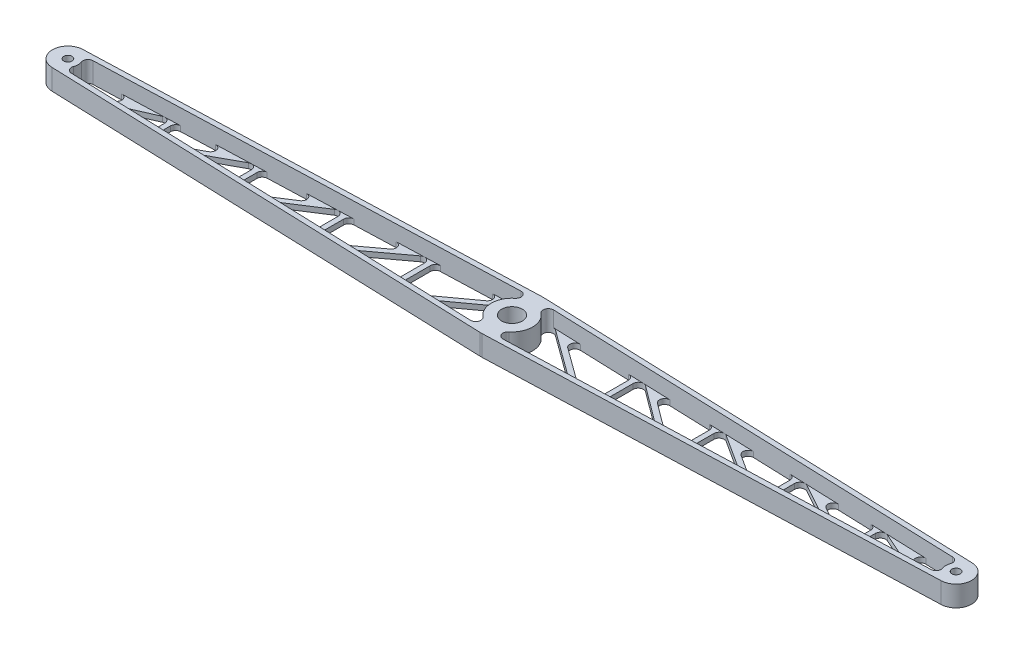
SolidWorks part; units mm, degrees
material "6061 Alloy"
ref_plane "Front Plane" through (0, 0, 0) normal (0, 0, 1) x (1, 0, 0)
ref_plane "Top Plane" through (0, 0, 0) normal (0, 1, 0) x (1, 0, 0)
ref_plane "Right Plane" through (0, 0, 0) normal (1, 0, 0) x (0, 0, -1)
sketch "Sketch1" plane through (0, 0, 0) normal (1, 0, 0) x (0, 0, -1)
  line L1 (-19.05, -6.35) -> (19.05, -6.35)
  line L2 (-19.05, -6.35) -> (-19.05, 6.35)
  line L3 (-19.05, 6.35) -> (19.05, 6.35)
  line L4 (19.05, -6.35) -> (19.05, 6.35)
  line L5 (-19.05, -6.35) -> (19.05, 6.35) construction
  line L6 (-19.05, 6.35) -> (19.05, -6.35) construction
  point P0 (0, 0)
  dimension "D1" = 38.1
  dimension "D2" = 12.7
extrude "Boss-Extrude1" add sketch "Sketch1" along normal mid plane 584.2
sketch "Sketch2" plane through (0, 6.35, 0) normal (0, 1, 0) x (1, 0, 0)
  circle A0 centre (0, 0) radius 6.35
  dimension "D1" = 12.7
extrude "Pivot Hole" cut sketch "Sketch2" against normal through all
hole_wizard "End Holes" positions "Sketch4" profile "Sketch3" tap size "1/4-20" standard "ANSI Inch" end condition through all
sketch "Sketch4" plane through (0, -6.35, 0) normal (0, -1, 0) x (-1, 0, 0)
  line L0 (273.05, 0) -> (292.1, 0) construction
  line L1 (292.1, -19.05) -> (292.1, 19.05) construction
  line L4 (-273.05, 0) -> (-292.1, 0) construction
  line L5 (-292.1, -19.05) -> (-292.1, 19.05) construction
  point P0 (273.05, 0)
  point P2 (-273.05, 0)
  dimension "D1" = 19.05
sketch "Sketch3" plane through (-273.05, -6.35, 0) normal (1, 0, 0) x (0, 0, -1)
  line L0 (0, 0) -> (0, 12.7)
  line L1 (0, 12.7) -> (2.5527, 12.7)
  line L2 (2.5527, 12.7) -> (2.5527, 0)
  line L5 (2.5527, 0) -> (0, 0)
  line L11 (0, -6.35) -> (0, 107.95) construction
  dimension "Thread Major Dia." = 5.1054
  dimension "Thru Tap Drill Depth" = 12.7
sketch "Sketch5" plane through (0, 6.35, 0) normal (0, 1, 0) x (1, 0, 0)
  line L0 (273.3823, -9.5192) -> (0.6645, -19.0384)
  line L1 (0.6645, 19.0384) -> (273.3823, 9.5192)
  line L2 (-0.6645, -19.0384) -> (-273.3823, -9.5192)
  line L3 (-273.3823, 9.5192) -> (-0.6645, 19.0384)
  line L8 (-292.1, 19.05) -> (-292.1, -19.05)
  line L9 (-292.1, -19.05) -> (292.1, -19.05)
  line L10 (292.1, -19.05) -> (292.1, 19.05)
  line L11 (292.1, 19.05) -> (-292.1, 19.05)
  line L12 (-292.1, 19.05) -> (-292.1, -19.05)
  line L13 (-292.1, -19.05) -> (292.1, -19.05)
  line L14 (292.1, -19.05) -> (292.1, 19.05)
  line L15 (292.1, 19.05) -> (-292.1, 19.05)
  arc A0 (273.3823, -9.5192) -> (273.3823, 9.5192) centre (273.05, 0) ccw
  arc A1 (-273.3823, -9.5192) -> (-273.3823, 9.5192) centre (-273.05, 0) cw
  arc A2 (0.6645, -19.0384) -> (-0.6645, -19.0384) centre (0, 0) cw
  arc A3 (-0.6645, 19.0384) -> (0.6645, 19.0384) centre (0, 0) cw
  line M8 (-292.1, 19.05) -> (-292.1, -19.05)
  line M9 (-292.1, -19.05) -> (292.1, -19.05)
  line M10 (292.1, -19.05) -> (292.1, 19.05)
  line M11 (292.1, 19.05) -> (-292.1, 19.05)
  dimension "D1" = 9.525
  dimension "D2" = 19.05
  dimension "D3" = 0
extrude "Profile Cut" cut sketch "Sketch5" against normal through all contours A3 L1 A0 L0 A2 L13 M11 M10 | L3 A3 L15 A2 L2 A1 M8 M9 region at (285.5207, 6.35, 0) region at (-146.05, 6.35, 16.1043)
sketch "Sketch7" plane through (0, 6.35, 0) normal (0, 1, 0) x (1, 0, 0)
  line L18 (0.5538, 15.8653) -> (273.2715, 6.3461)
  line L19 (10.073, 15.5331) -> (264.2967, 6.6594)
  line L25 (273.2715, -6.3461) -> (0.5538, -15.8653)
  line L26 (264.2967, -6.6594) -> (10.073, -15.5331)
  line L28 (-0.5538, -15.8653) -> (-273.2715, -6.3461)
  line L29 (-10.073, -15.5331) -> (-264.2967, -6.6594)
  line L31 (-273.2715, 6.3461) -> (-0.5538, 15.8653)
  line L32 (-264.2967, 6.6594) -> (-10.073, 15.5331)
  arc A0 (267.1406, 2.3242) -> (267.1406, -2.3242) centre (273.05, 0) ccw
  arc A1 (-267.1406, -2.3242) -> (-267.1406, 2.3242) centre (-273.05, 0) ccw
  arc A2 (7.9698, 9.888) -> (7.9698, -9.888) centre (0, 0) cw
  arc A3 (-7.9698, 9.888) -> (-7.9698, -9.888) centre (0, 0) ccw
  arc A4 (-267.1406, 2.3242) -> (-264.2967, 6.6594) centre (-264.186, 3.4863) cw
  arc A5 (-264.2967, -6.6594) -> (-267.1406, -2.3242) centre (-264.186, -3.4863) cw
  arc A6 (267.1406, -2.3242) -> (264.2967, -6.6594) centre (264.186, -3.4863) cw
  arc A7 (264.2967, 6.6594) -> (267.1406, 2.3242) centre (264.186, 3.4863) cw
  arc A8 (10.073, 15.5331) -> (7.9698, 9.888) centre (9.9622, 12.36) ccw
  arc A9 (7.9698, -9.888) -> (10.073, -15.5331) centre (9.9622, -12.36) ccw
  arc A10 (-7.9698, -9.888) -> (-10.073, -15.5331) centre (-9.9622, -12.36) cw
  arc A11 (-10.073, 15.5331) -> (-7.9698, 9.888) centre (-9.9622, 12.36) cw
  dimension "D5" = 6.35
  dimension "D6" = 3.175
  dimension "D7" = 12.7
  dimension "D1" = 3.175
  dimension "D2" = 3.175
  dimension "D3" = 3.175
  dimension "D4" = 3.175
extrude "Pocket" cut sketch "Sketch7" against normal offset from surface (9.525 mm away) 3.175 up to face at (-273.05, -6.35, -2.5527)
sketch "Sketch6" plane through (0, 6.35, 0) normal (0, 1, 0) x (1, 0, 0)
  line L0 (0, 19.05) -> (0, -19.05) construction
  line L1 (0, 15.8847) -> (-273.3823, 6.3423) construction
  line L2 (0, -15.8847) -> (-273.3823, -6.3423) construction
  line L3 (-273.3823, 9.5192) -> (-0.6645, 19.0384) construction
  line L4 (-0.6645, -19.0384) -> (-273.3823, -9.5192) construction
  line L5 (-136.6911, 11.1135) -> (-136.8019, 14.2865) construction
  line L6 (-136.6911, -11.1135) -> (-136.8019, -14.2865) construction
  line L7 (-273.3823, 9.5192) -> (-273.3823, -9.5192) construction
  line L8 (-44.2165, -8.6633) -> (-11.8316, 14.9263)
  line L9 (-262.8989, -6.3888) -> (-245.8319, 1.1796)
  line L10 (-247.2297, 7.2551) -> (-264.2967, 6.6594)
  line L11 (-243.6911, -1.3442) -> (-222.9021, 7.8747)
  line L12 (-218.44, 4.9723) -> (-218.44, -4.9723)
  line L13 (-221.7258, -8.1453) -> (-242.5148, -7.4197)
  line L14 (-245.8319, 1.1796) -> (-244.5448, -1.7228) construction
  line L15 (-215.265, 5.3047) -> (-215.265, -5.3047)
  line L16 (-210.5661, -8.0901) -> (-189.8531, 3.2424)
  line L17 (-191.4878, 9.2008) -> (-212.2008, 8.4778)
  line L18 (-194.9594, -3.1705) -> (-171.7039, 9.553)
  line L19 (-167.005, 6.7676) -> (-167.005, -6.7676)
  line L20 (-170.2908, -9.9407) -> (-193.5462, -9.1289)
  line L21 (-189.8531, 3.2424) -> (-188.3292, 0.457) construction
  line L22 (-218.44, 0) -> (-215.265, 0) construction
  line L23 (-10.073, -15.5331) -> (-42.4579, -14.4027)
  line L24 (-60.96, -10.6908) -> (-60.96, 10.6908)
  line L25 (-57.8958, 13.8638) -> (-27.0649, 14.94)
  line L26 (-25.0848, 9.2006) -> (-55.9156, -13.2571)
  line L27 (-25.0848, 9.2006) -> (-23.2154, 6.6342) construction
  line L28 (-163.83, 7.1001) -> (-163.83, -7.1001)
  line L29 (-158.9358, -9.7694) -> (-135.6247, 5.2445)
  line L30 (-137.4546, 11.0868) -> (-160.7658, 10.2731)
  line L31 (-145.6876, -5.0132) -> (-120.4642, 11.2322)
  line L32 (-115.57, 8.5629) -> (-115.57, -8.5629)
  line L33 (-118.8558, -11.736) -> (-144.0792, -10.8556)
  line L34 (-135.6247, 5.2445) -> (-133.9055, 2.5752) construction
  line L35 (-167.005, 0) -> (-163.83, 0) construction
  line L36 (-266.7, 0) -> (-218.44, 0) construction
  line L37 (-215.265, 0) -> (-167.005, 0) construction
  line L38 (-163.83, 0) -> (-115.57, 0) construction
  line L39 (-60.96, 0) -> (-12.7, 0) construction
  line L40 (-115.57, 0) -> (-112.395, 0) construction
  line L41 (-64.135, 0) -> (-60.96, 0) construction
  line L42 (-112.395, 8.8954) -> (-112.395, -8.8954)
  line L43 (-107.3273, -11.4446) -> (-82.1837, 7.2239)
  line L44 (-84.1872, 12.9461) -> (-109.3308, 12.0685)
  line L45 (-95.852, -6.8789) -> (-69.2027, 12.9075)
  line L46 (-64.135, 10.3583) -> (-64.135, -10.3583)
  line L47 (-67.4208, -13.5313) -> (-94.07, -12.6012)
  line L48 (-82.1837, 7.2239) -> (-80.291, 4.6747) construction
  line L49 (-112.395, 0) -> (-64.135, 0) construction
  arc A0 (-0.6645, -19.0384) -> (0.6645, -19.0384) centre (0, 0) ccw construction
  arc A1 (0.6645, 19.0384) -> (-0.6645, 19.0384) centre (0, 0) ccw construction
  arc A2 (-245.8319, 1.1796) -> (-247.2297, 7.2551) centre (-247.1189, 4.0821) ccw
  arc A3 (-267.1406, -2.3242) -> (-262.8989, -6.3888) centre (-264.186, -3.4863) ccw
  arc A4 (-267.1406, 2.3242) -> (-264.2967, 6.6594) centre (-264.186, 3.4863) cw
  arc A5 (-267.1406, 2.3242) -> (-267.1406, -2.3242) centre (-273.05, 0) cw
  arc A6 (-218.44, -4.9723) -> (-221.7258, -8.1453) centre (-221.615, -4.9723) cw
  arc A7 (-222.9021, 7.8747) -> (-218.44, 4.9723) centre (-221.615, 4.9723) cw
  arc A8 (-243.6911, -1.3442) -> (-242.5148, -7.4197) centre (-242.404, -4.2466) ccw
  arc A9 (-189.8531, 3.2424) -> (-191.4878, 9.2008) centre (-191.377, 6.0277) ccw
  arc A10 (-215.265, -5.3047) -> (-210.5661, -8.0901) centre (-212.09, -5.3047) ccw
  arc A11 (-215.265, 5.3047) -> (-212.2008, 8.4778) centre (-212.09, 5.3047) cw
  arc A12 (-167.005, -6.7676) -> (-170.2908, -9.9407) centre (-170.18, -6.7676) cw
  arc A13 (-171.7039, 9.553) -> (-167.005, 6.7676) centre (-170.18, 6.7676) cw
  arc A14 (-194.9594, -3.1705) -> (-193.5462, -9.1289) centre (-193.4354, -5.9559) ccw
  arc A15 (-7.9698, 9.888) -> (-7.9698, -9.888) centre (0, 0) ccw
  arc A16 (-44.2165, -8.6633) -> (-42.4579, -14.4027) centre (-42.3471, -11.2296) ccw
  arc A17 (-7.9698, -9.888) -> (-10.073, -15.5331) centre (-9.9622, -12.36) cw
  arc A18 (-7.9698, 9.888) -> (-11.8316, 14.9263) centre (-9.9622, 12.36) ccw
  arc A19 (-60.96, 10.6908) -> (-57.8958, 13.8638) centre (-57.785, 10.6908) cw
  arc A20 (-60.96, -10.6908) -> (-55.9156, -13.2571) centre (-57.785, -10.6908) ccw
  arc A21 (-25.0848, 9.2006) -> (-27.0649, 14.94) centre (-26.9541, 11.7669) ccw
  arc A22 (-135.6247, 5.2445) -> (-137.4546, 11.0868) centre (-137.3438, 7.9138) ccw
  arc A23 (-163.83, -7.1001) -> (-158.9358, -9.7694) centre (-160.655, -7.1001) ccw
  arc A24 (-163.83, 7.1001) -> (-160.7658, 10.2731) centre (-160.655, 7.1001) cw
  arc A25 (-115.57, -8.5629) -> (-118.8558, -11.736) centre (-118.745, -8.5629) cw
  arc A26 (-120.4642, 11.2322) -> (-115.57, 8.5629) centre (-118.745, 8.5629) cw
  arc A27 (-145.6876, -5.0132) -> (-144.0792, -10.8556) centre (-143.9685, -7.6825) ccw
  arc A28 (-82.1837, 7.2239) -> (-84.1872, 12.9461) centre (-84.0764, 9.7731) ccw
  arc A29 (-112.395, -8.8954) -> (-107.3273, -11.4446) centre (-109.22, -8.8954) ccw
  arc A30 (-112.395, 8.8954) -> (-109.3308, 12.0685) centre (-109.22, 8.8954) cw
  arc A31 (-64.135, -10.3583) -> (-67.4208, -13.5313) centre (-67.31, -10.3583) cw
  arc A32 (-69.2027, 12.9075) -> (-64.135, 10.3583) centre (-67.31, 10.3583) cw
  arc A33 (-95.852, -6.8789) -> (-94.07, -12.6012) centre (-93.9593, -9.4281) ccw
  dimension "D2" = 3.175
  dimension "D3" = 6.35
  dimension "D4" = 3.175
  dimension "D5" = 3.175
  dimension "D6" = 12.7
  dimension "D7" = 3.175
  dimension "D8" = 3.175
  dimension "D1" = 3.175
extrude "Skeleton" cut sketch "Sketch6" against normal through all
mirror "Mirror1" about plane through (0, 0, 0) normal (1, 0, 0) of "Skeleton"
